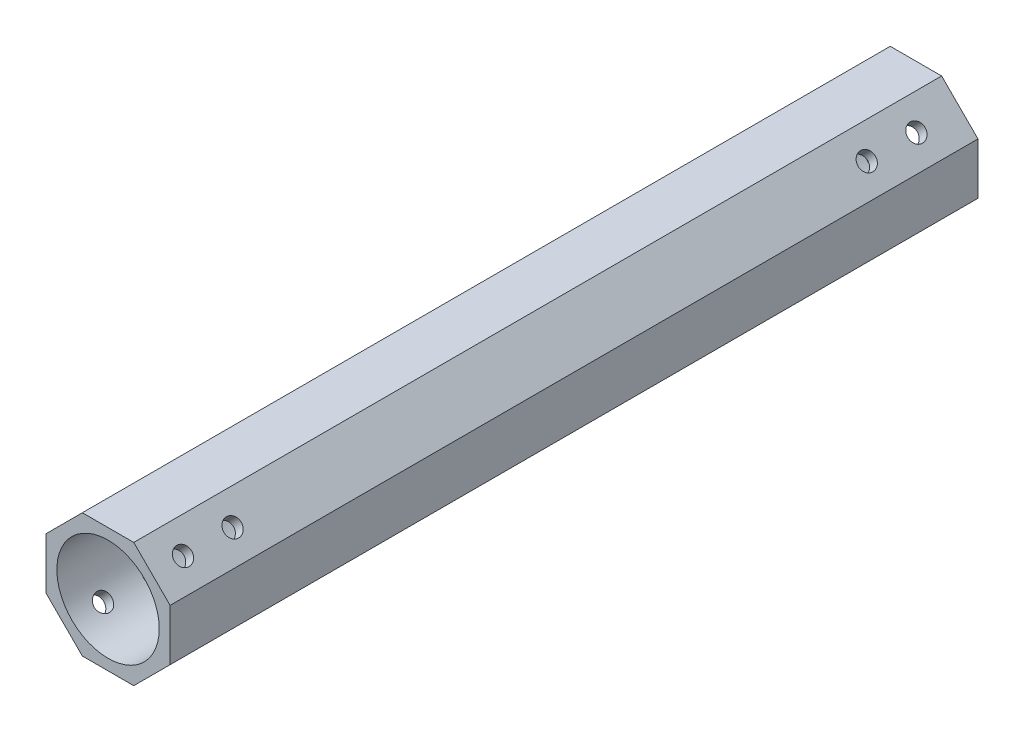
SolidWorks part; units mm, degrees
ref_plane "Front Plane" through (0, 0, 0) normal (0, 0, 1) x (1, 0, 0)
ref_plane "Top Plane" through (0, 0, 0) normal (0, 1, 0) x (1, 0, 0)
ref_plane "Right Plane" through (0, 0, 0) normal (1, 0, 0) x (0, 0, -1)
sketch "Sketch1" plane through (0, 0, 0) normal (0, 0, 1) x (1, 0, 0)
  line L6 (10, 4.1421) -> (4.1421, 10)
  line L7 (4.1421, 10) -> (-4.1421, 10)
  line L8 (-4.1421, 10) -> (-10, 4.1421)
  line L9 (-10, 4.1421) -> (-10, -4.1421)
  line L10 (-10, -4.1421) -> (-4.1421, -10)
  line L11 (-4.1421, -10) -> (4.1421, -10)
  line L12 (4.1421, -10) -> (10, -4.1421)
  line L13 (10, -4.1421) -> (10, 4.1421)
  circle A0 centre (0, 0) radius 8.25
  circle A1 centre (0, 0) radius 10 construction
  dimension "D1" = 16.5
  dimension "D2" = 20
extrude "Boss-Extrude1" add sketch "Sketch1" against normal up to surface (128.2 mm away)
sketch "Sketch2" plane through (0, 0, -128.2) normal (0, 0, -1) x (-1, 0, 0)
  line L8 (-10, 4.1421) -> (-10, -4.1421)
  line L9 (-10, -4.1421) -> (-4.1421, -10)
  line L10 (-4.1421, -10) -> (4.1421, -10)
  line L11 (4.1421, -10) -> (10, -4.1421)
  line L12 (10, -4.1421) -> (10, 4.1421)
  line L13 (10, 4.1421) -> (4.1421, 10)
  line L14 (4.1421, 10) -> (-4.1421, 10)
  line L15 (-4.1421, 10) -> (-10, 4.1421)
  line L16 (-10, 4.1421) -> (-10, -4.1421)
  line L17 (-10, -4.1421) -> (-4.1421, -10)
  line L18 (-4.1421, -10) -> (4.1421, -10)
  line L19 (4.1421, -10) -> (10, -4.1421)
  line L20 (10, -4.1421) -> (10, 4.1421)
  line L21 (10, 4.1421) -> (4.1421, 10)
  line L22 (4.1421, 10) -> (-4.1421, 10)
  line L23 (-4.1421, 10) -> (-10, 4.1421)
  dimension "D1" = 0
extrude "Boss-Extrude2" add sketch "Sketch2" along normal blind 2
sketch "Sketch6" plane through (-7.0711, 7.0711, 0) normal (-0.7071, 0.7071, 0) x (0, 0, 1)
  circle A0 centre (-13, 0) radius 1.4 construction
  circle A1 centre (-5, 0) radius 1.4 construction
  circle A2 centre (-13, 0) radius 1.4
  circle A3 centre (-5, 0) radius 1.4
  circle A4 centre (-115.2, 0) radius 1.4 construction
  circle A5 centre (-123.2, 0) radius 1.4 construction
  circle A6 centre (-115.2, 0) radius 1.4
  circle A7 centre (-123.2, 0) radius 1.4
extrude "Cut-Extrude2" cut sketch "Sketch6" against normal through all
ref_axis "Axis1" through (0, 0, 6.85) along (0, 0, -1)
pattern_circular "CirPattern1" count 2 every 270 about axis through (0, 0, 6.85) along (0, 0, -1) of "Cut-Extrude2"
sketch "Sketch7" plane through (0, 0, -130.2) normal (0, 0, -1) x (-1, 0, 0)
  circle A0 centre (0, 0) radius 6.2698
extrude "Cut-Extrude3" cut sketch "Sketch7" against normal through all
